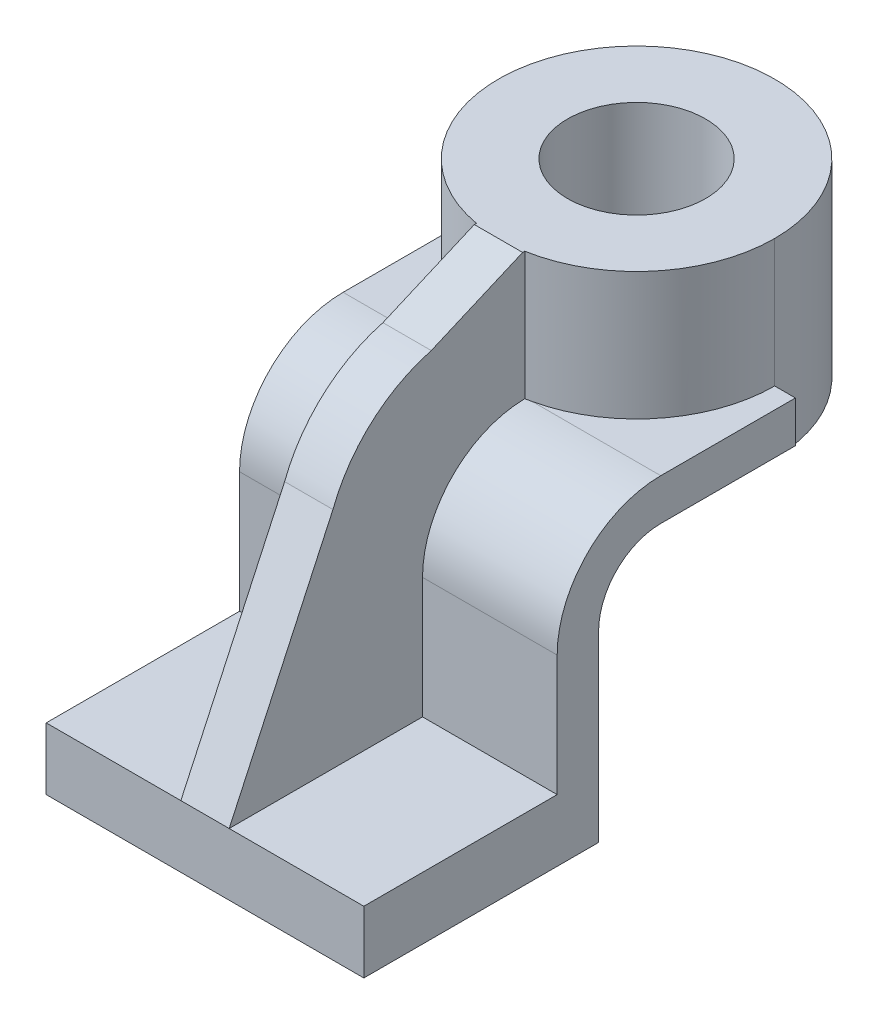
SolidWorks part; units mm, degrees
ref_plane "Front Plane" through (0, 0, 0) normal (0, 0, 1) x (1, 0, 0)
ref_plane "Top Plane" through (0, 0, 0) normal (0, 1, 0) x (1, 0, 0)
ref_plane "Right Plane" through (0, 0, 0) normal (1, 0, 0) x (0, 0, -1)
sketch "Sketch1" plane through (0, 0, 0) normal (0, 1, 0) x (1, 0, 0)
  line L1 (-46, 34) -> (46, 34)
  line L2 (-46, 34) -> (-46, -34)
  line L3 (-46, -34) -> (46, -34)
  line L4 (46, 34) -> (46, -34)
  line L5 (-46, 34) -> (46, -34) construction
  line L6 (-46, -34) -> (46, 34) construction
  point P0 (0, 0)
  dimension "D1" = 68
  dimension "D2" = 92
extrude "Boss-Extrude1" add sketch "Sketch1" along normal blind 18
sketch "Sketch2" plane through (46, 0, 0) normal (1, 0, 0) x (0, 0, -1)
  line L0 (34, 18) -> (34, 71) construction
  line L1 (-34, 0) -> (91, 0) construction
  line L2 (34, 18) -> (34, 53)
  line L3 (52, 71) -> (91, 71)
  line L4 (22, 18) -> (22, 53)
  line L5 (52, 83) -> (91, 83)
  line L6 (34, 18) -> (22, 18)
  line L7 (91, 71) -> (91, 83)
  arc A0 (34, 53) -> (52, 71) centre (52, 53) cw
  arc A1 (22, 53) -> (52, 83) centre (52, 53) cw
  dimension "D3" = 18
  dimension "D1" = 53
  dimension "D2" = 125
  dimension "D4" = 53
  dimension "D5" = 12
extrude "Boss-Extrude2" add sketch "Sketch2" against normal blind 92
sketch "Sketch3" plane through (0, 83, 0) normal (0, 1, 0) x (1, 0, 0)
  line L0 (-46, 91) -> (46, 91) construction
  circle A0 centre (0, 91) radius 40
  circle A1 centre (0, 91) radius 20
  dimension "D1" = 80
  dimension "D2" = 40
extrude "Boss-Extrude3" add sketch "Sketch3" against normal blind 18 and the other way blind 37
extrude "Cut-Extrude1" cut sketch "Sketch3<2>" against normal blind 18 contours A1
sketch "Sketch3<2>" plane through (0, 83, 0) normal (0, 1, 0) x (1, 0, 0) same geometry as "Sketch3"
sketch "Sketch4" plane through (0, 0, 0) normal (1, 0, 0) x (0, 0, -1)
  line L0 (-34, 18) -> (22, 18) construction
  line L1 (22, 53) -> (22, 18) construction
  line L2 (-34, 18) -> (22, 18)
  line L3 (22, 53) -> (22, 18)
  line L4 (-34, 18) -> (-3.9465, 82.9833)
  line L5 (24.5327, 108.6241) -> (51, 120)
  line L7 (51, 82.9833) -> (-3.9465, 82.9833) construction
  line L9 (56, 120) -> (56, 82.9833)
  line L10 (56, 120) -> (51, 120)
  line L11 (56, 82.9833) -> (51, 82.9833)
  arc A0 (52, 83) -> (22, 53) centre (52, 53) ccw construction
  arc A1 (51, 82.9833) -> (22, 53) centre (52, 53) ccw
  arc A3 (24.5327, 108.6241) -> (-3.9465, 82.9833) centre (35.3006, 68.0279) ccw
  dimension "D2" = 42
extrude "Boss-Extrude6" add sketch "Sketch4" along normal mid plane 14
